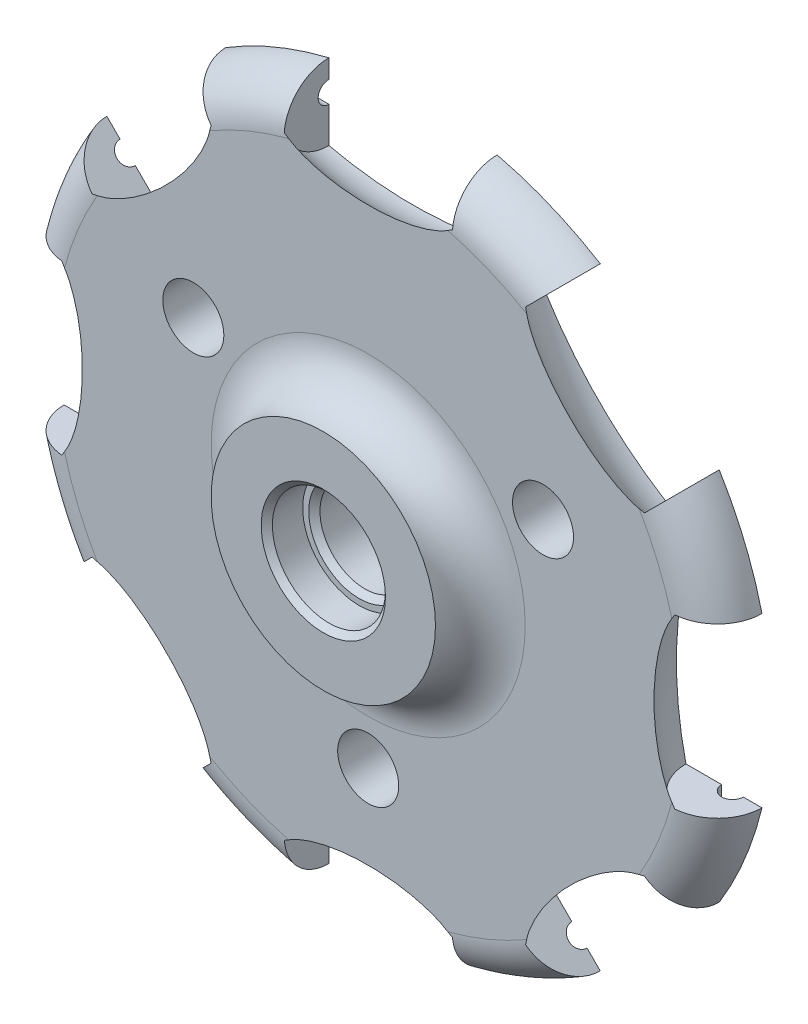
SolidWorks part; units mm, degrees
ref_plane "Front Plane" through (0, 0, 0) normal (0, 0, 1) x (1, 0, 0)
ref_plane "Top Plane" through (0, 0, 0) normal (0, 1, 0) x (1, 0, 0)
ref_plane "Right Plane" through (0, 0, 0) normal (1, 0, 0) x (0, 0, -1)
sketch "Sketch1" plane through (0, 0, 0) normal (0, 0, 1) x (1, 0, 0)
  circle A0 centre (0, 0) radius 25.4
  dimension "D1" = 50.8
extrude "Boss-Extrude1" add sketch "Sketch1" along normal blind 3.175
fillet "Fillet1" radius 3.1852 1 edges at (25.4, 0, 3.175)
sketch "Sketch7" plane through (0, 0, 3.175) normal (0, 0, 1) x (1, 0, 0)
  circle A0 centre (0, 0) radius 7.9375
  dimension "D1" = 15.875
extrude "Boss-Extrude2" add sketch "Sketch7" along normal blind 3.175
sketch "Sketch2" plane through (0, 0, 6.35) normal (0, 0, 1) x (1, 0, 0)
  circle A0 centre (0, -14.2875) radius 2.159
  circle A1 centre (-12.3733, 7.1437) radius 2.159
  circle A2 centre (12.3733, 7.1438) radius 2.159
  circle A3 centre (0, 0) radius 3.175
  point P9 (0, 0)
  dimension "D2" = 4.318
  dimension "D4" = 6.35
  dimension "D1" = 14.2875
  dimension "D3" = 3
extrude "Cut-Extrude1" cut sketch "Sketch2" against normal through all
sketch "Sketch5" plane through (0, 0, 0) normal (0, 0, 1) x (1, 0, 0)
  line L0 (-5.9531, 22.606) -> (5.9531, 22.606)
  line L1 (5.9531, 22.606) -> (5.9531, 25.8994)
  line L2 (-5.9531, 22.606) -> (-5.9531, 25.8994)
  line L3 (-5.9531, 22.606) -> (-8.5086, 22.606) construction
  arc A0 (-5.9531, 25.8994) -> (5.9531, 25.8994) centre (0, 0) cw
  circle A1 centre (0, 0) radius 25.4 construction
  point P5 (0, 22.606)
  point P9 (0, 26.5748)
  dimension "D1" = 11.9062
  dimension "D2" = 22.606
  dimension "D3" = 7.9375
revolve "Cut-Revolve1" cut sketch "Sketch5" angle 360 about L3
sketch "Sketch6" plane through (0, 0, 0) normal (1, 0, 0) x (0, 0, -1)
  line L0 (0, -25.4) -> (0, 24.6925) construction
  circle A0 centre (0, 22.606) radius 0.762
  arc A1 (-3.163, 21.6886) -> (0, 19.3126) centre (0, 22.606) ccw construction
  dimension "D1" = 1.524
extrude "Cut-Extrude2" cut sketch "Sketch6" against normal mid plane 15.24
pattern_circular "CirPattern1" count 8 over 360 about axis through (0, 0, 0) along (0, 0, 1) of "Cut-Revolve1", "Cut-Extrude2"
sketch "Sketch8" plane through (0, 0, 6.35) normal (0, 0, 1) x (1, 0, 0)
  circle A0 centre (0, 0) radius 4.0005
  dimension "D1" = 8.001
extrude "Cut-Extrude3" cut sketch "Sketch8" against normal blind 2.54
chamfer "Chamfer1" distance 0.3969 angle 45 2 edges at (4.0005, 0, 6.35) (3.175, 0, 3.81)
fillet "Fillet2" radius 3.175 1 edges at (7.9375, 0, 3.175)
